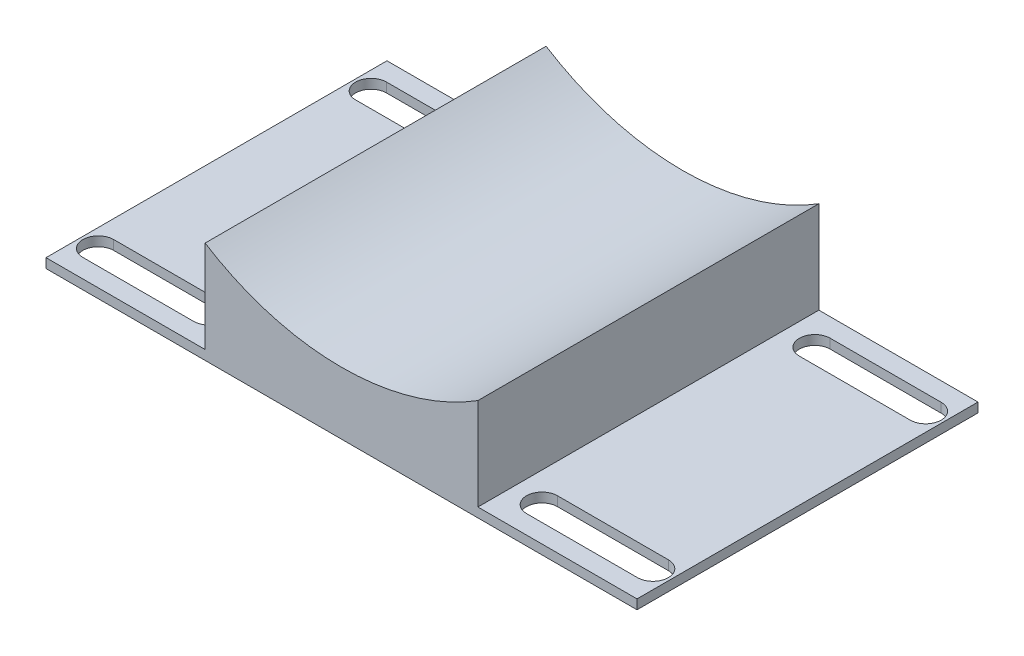
SolidWorks part; units mm, degrees
ref_plane "Front Plane" through (0, 0, 0) normal (0, 0, 1) x (1, 0, 0)
ref_plane "Top Plane" through (0, 0, 0) normal (0, 1, 0) x (1, 0, 0)
ref_plane "Right Plane" through (0, 0, 0) normal (1, 0, 0) x (0, 0, -1)
sketch "Sketch2" plane through (0, 0, 0) normal (0, 0, 1) x (1, 0, 0)
  line L0 (38.1, 1.3208) -> (82.55, 1.3208)
  line L1 (-82.55, 1.3208) -> (-38.1, 1.3208)
  line L2 (-82.55, 1.3208) -> (-82.55, -1.3208)
  line L3 (-82.55, -1.3208) -> (82.55, -1.3208)
  line L4 (82.55, 1.3208) -> (82.55, -1.3208)
  line L5 (-82.55, 1.3208) -> (82.55, -1.3208) construction
  line L6 (-82.55, -1.3208) -> (82.55, 1.3208) construction
  line L8 (-38.1, 27.0748) -> (-38.1, 1.3208)
  line L10 (38.1, 27.0748) -> (38.1, 1.3208)
  arc A0 (-38.1, 27.0748) -> (38.1, 27.0748) centre (0, 87.5792) ccw
  point P0 (0, 0)
  point P7 (0, 0)
  point P8 (0, 0)
  dimension "D3" = 143.002
  dimension "D1" = 2.6416
  dimension "D2" = 165.1
  dimension "D4" = 88.9
  dimension "D5" = 0
  dimension "D6" = 38.1
  dimension "D7" = 38.1
extrude "Boss-Extrude1" add sketch "Sketch2" along normal blind 95.25
sketch "Sketch3" plane through (0, 1.3208, 0) normal (0, 1, 0) x (1, 0, 0)
  line L0 (-77.47, -9.525) -> (-46.482, -9.525) construction
  line L1 (-77.47, -5.207) -> (-46.482, -5.207)
  line L2 (-77.47, -13.843) -> (-46.482, -13.843)
  line L3 (-38.1, 0) -> (-82.55, 0) construction
  line L4 (0, 0) -> (0, -112.7415) construction
  line L5 (-77.47, -85.725) -> (-46.482, -85.725) construction
  line L6 (-77.47, -81.407) -> (-46.482, -81.407)
  line L7 (-77.47, -90.043) -> (-46.482, -90.043)
  arc A0 (-77.47, -5.207) -> (-77.47, -13.843) centre (-77.47, -9.525) ccw
  arc A1 (-46.482, -13.843) -> (-46.482, -5.207) centre (-46.482, -9.525) ccw
  arc A2 (-77.47, -81.407) -> (-77.47, -90.043) centre (-77.47, -85.725) ccw
  arc A3 (-46.482, -90.043) -> (-46.482, -81.407) centre (-46.482, -85.725) ccw
  point P2 (-61.976, -9.525)
  point P14 (-61.976, -85.725)
  point P19 (0, 0)
  point P21 (-39.9412, -85.725)
  dimension "D1" = 61.976
  dimension "D2" = 30.988
  dimension "D3" = 8.636
  dimension "D4" = 9.525
  dimension "D5" = 8.636
  dimension "D6" = 76.2
  dimension "D7" = 30.988
extrude "Cut-Extrude1" cut sketch "Sketch3" against normal blind 95.25
mirror "Mirror2" about plane through (0, 0, 0) normal (1, 0, 0) of "Cut-Extrude1"
